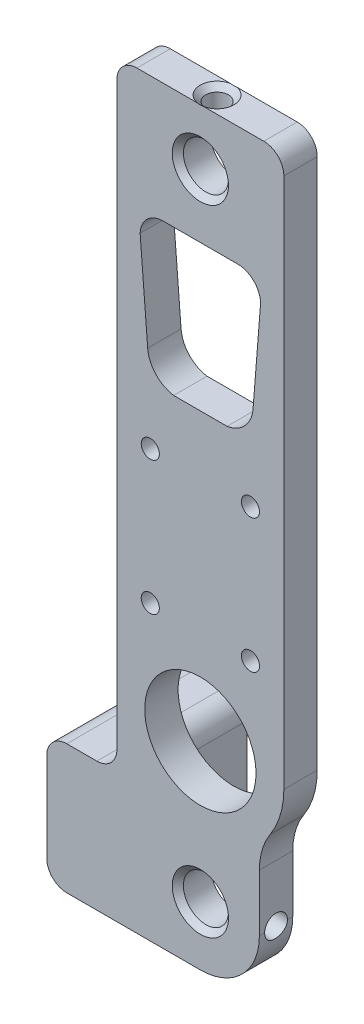
SolidWorks part; units mm, degrees
material "ABS"
ref_plane "Front Plane" through (0, 0, 0) normal (0, 0, 1) x (1, 0, 0)
ref_plane "Top Plane" through (0, 0, 0) normal (0, 1, 0) x (1, 0, 0)
ref_plane "Right Plane" through (0, 0, 0) normal (1, 0, 0) x (0, 0, -1)
sketch "Sketch1" plane through (0, 0, 0) normal (0, 0, 1) x (1, 0, 0)
  line L1 (-9, -12) -> (9, -12) construction
  line L2 (-9, -12) -> (-9, 12) construction
  line L3 (-9, 12) -> (9, 12) construction
  line L4 (9, -12) -> (9, 12) construction
  line L5 (-9, -12) -> (9, 12) construction
  line L6 (-9, 12) -> (9, -12) construction
  line L7 (-15, 17) -> (15, 17)
  line L8 (-15, 17) -> (-15, -17)
  line L9 (-15, -17) -> (15, -17)
  line L10 (15, 17) -> (15, -17)
  line L11 (-15, 17) -> (15, -17) construction
  line L12 (-15, -17) -> (15, 17) construction
  circle A0 centre (-9, 12) radius 1.625
  circle A1 centre (9, 12) radius 1.625
  circle A2 centre (-9, -12) radius 1.625
  circle A3 centre (9, -12) radius 1.625
  point P0 (0, 0)
  point P6 (0, 0)
  dimension "D5" = 3.25
  dimension "D1" = 30
  dimension "D2" = 34
  dimension "D3" = 5
  dimension "D4" = 6
extrude "Boss-Extrude1" add sketch "Sketch1" against normal blind 6
sketch "Sketch2" plane through (0, 0, 0) normal (0, 0, 1) x (1, 0, 0)
  line L1 (-15, -17) -> (15, -17)
  line L2 (-15, -17) -> (-15, -41.4)
  line L3 (-15, -64.6) -> (15, -64.6)
  line L4 (15, -17) -> (15, -64.6)
  line L5 (15, -17) -> (15, 17) construction
  line L11 (-15, -64.6) -> (-27.6, -64.6)
  line L13 (-15, -41.4) -> (-27.6, -41.4)
  line L14 (-27.6, -64.6) -> (-27.6, -41.4)
  circle A0 centre (0, -29) radius 10
  circle A1 centre (0, -54) radius 4.05
  circle A3 centre (0, -54) radius 4 construction
  circle A4 centre (0, -29) radius 9.36 construction
  dimension "D2" = 20
  dimension "D3" = 8.1
  dimension "D1" = 47.6
  dimension "D4" = 23.2
  dimension "D5" = 12.6
extrude "Boss-Extrude3" add sketch "Sketch2" along normal up to surface (-6 mm away) up to face at (10.625, -12, -6)
sketch "Sketch3" plane through (0, 0, -6) normal (0, 0, -1) x (-1, 0, 0)
  line L0 (19.7, -64.6) -> (24, -64.6) construction
  line L1 (27.6, -61) -> (27.6, -45) construction
  line L2 (24, -41.4) -> (19.7, -41.4) construction
  line L3 (19.7, -64.6) -> (24, -64.6)
  line L4 (27.6, -61) -> (27.6, -45)
  line L5 (24, -41.4) -> (19.7, -41.4)
  line L6 (19.7, -41.4) -> (19.7, -64.6)
  arc A0 (24, -64.6) -> (27.6, -61) centre (24, -61) ccw construction
  arc A1 (27.6, -45) -> (24, -41.4) centre (24, -45) ccw construction
  arc A2 (24, -64.6) -> (27.6, -61) centre (24, -61) ccw
  arc A3 (27.6, -45) -> (24, -41.4) centre (24, -45) ccw
  circle A4 centre (24, -45) radius 2.4 construction
  circle A5 centre (24, -45) radius 2.4 construction
  circle A6 centre (24, -61) radius 2.4 construction
  circle A7 centre (24, -61) radius 2.4 construction
  circle A8 centre (24, -45) radius 2.1
  circle A9 centre (24, -61) radius 2.1
  dimension "D1" = 4.2
  dimension "D2" = 23.2
extrude "Boss-Extrude4" add sketch "Sketch3" along normal up to surface (21.3764 mm away) contours L4 A3 L5 L6 L3 A2 A9 A8 region at (-23.4687, -53, -6)
sketch "Sketch4" plane through (0, 0, -6) normal (0, 0, -1) x (-1, 0, 0)
  line L2 (24, -64.6) -> (27.6, -64.6)
  line L3 (24, -64.6) -> (27.6, -64.6)
  line L4 (27.6, -64.6) -> (27.6, -61)
  line L5 (24, -41.4) -> (19.7, -41.4)
  line L6 (27.6, -45) -> (27.6, -41.4)
  line L7 (27.6, -45) -> (27.6, -41.4)
  line L9 (19.7, -41.4) -> (19.7, -64.6)
  line L11 (27.6, -61) -> (27.6, -45)
  line L13 (19.7, -41.4) -> (19.7, -64.6)
  line L15 (27.6, -61) -> (27.6, -45)
  line L18 (27.6, -64.6) -> (27.6, -61)
  line L19 (27.6, -41.4) -> (24, -41.4)
  line L22 (24, -41.4) -> (19.7, -41.4)
  line L24 (27.6, -41.4) -> (24, -41.4)
  line L27 (19.7, -64.6) -> (24, -64.6)
  line L30 (19.7, -64.6) -> (24, -64.6)
  arc A1 (24, -64.6) -> (27.6, -61) centre (24, -61) ccw
  arc A2 (24, -64.6) -> (27.6, -61) centre (24, -61) ccw
  arc A3 (27.6, -45) -> (24, -41.4) centre (24, -45) ccw
  arc A4 (27.6, -45) -> (24, -41.4) centre (24, -45) ccw
  arc A5 (24, -64.6) -> (27.6, -61) centre (24, -61) ccw
  arc A6 (27.6, -45) -> (24, -41.4) centre (24, -45) ccw
  arc A7 (24, -64.6) -> (27.6, -61) centre (24, -61) ccw
  arc A9 (27.6, -45) -> (24, -41.4) centre (24, -45) ccw
  arc M13 (27.6, -61) -> (24, -64.6) centre (24, -61) cw
  line M14 (24, -64.6) -> (27.6, -64.6)
  line M15 (27.6, -64.6) -> (27.6, -61)
  dimension "D1" = 0
  dimension "D2" = 0
  dimension "D3" = 0
extrude "Cut-Extrude1" cut sketch "Sketch4" against normal blind 10 contours A6 L7 L24 | M15 M13 M14 region at (-26.7959, -63.7959, -6) region at (-26.7959, -42.2041, -6)
sketch "Sketch5" plane through (0, 0, -6) normal (0, 0, -1) x (-1, 0, 0)
  line L0 (-15, -64.6) -> (19.7, -64.6) construction
  line L1 (19.7, -41.4) -> (15, -41.4)
  line L2 (19.7, -41.4) -> (19.7, -64.6)
  line L3 (19.7, -64.6) -> (15, -64.6)
  line L4 (15, -41.4) -> (15, -64.6)
  line L6 (15, 17) -> (15, -41.4) construction
  line L7 (19.7, -41.4) -> (15, -41.4) construction
  line L8 (19.7, -41.4) -> (19.7, -64.6) construction
  line M3 (19.7, -64.6) -> (19.7, -41.4)
  line M8 (-15, -64.6) -> (19.7, -64.6)
extrude "Boss-Extrude5" add sketch "Sketch5" along normal up to surface (17.3764 mm away) contours L1 L4 M8 M3 region at (-17.35, -53, -6)
sketch "Sketch7" plane through (0, 0, -6) normal (0, 0, -1) x (-1, 0, 0)
  line L0 (-15, -64.6) -> (-15, 17) construction
  line L3 (-10.6, -54) -> (-10.6, -43.7563)
  line L4 (-15, -64.6) -> (15, -64.6) construction
  arc A1 (-10.6, -43.7563) -> (-12.5505, -37.2149) centre (-22.5443, -43.7563) ccw
  circle A2 centre (0, -29) radius 10 construction
  circle A3 centre (0, -29) radius 15
  circle A6 centre (0, -54) radius 10.6
  line M12 (-15, 17) -> (-15, -64.6)
  line M13 (-15, -64.6) -> (15, -64.6)
extrude "Cut-Extrude2" cut sketch "Sketch7" against normal blind 10 contours A6 L3 A1 A3 M12 M13 region at (12.161, -52.411, -6)
sketch "Sketch8" plane through (10.6, 0, 0) normal (1, 0, 0) x (0, 0, -1)
  line L0 (0, -54) -> (6, -54) construction
  circle A0 centre (3, -54) radius 2.05
  dimension "D1" = 4.1
extrude "Cut-Extrude3" cut sketch "Sketch8" against normal blind 10
sketch "Sketch9" plane through (0, 0, 0) normal (0, 0, 1) x (1, 0, 0)
  line L0 (15, -29) -> (15, 17) construction
  line L1 (-15, 17) -> (15, 17)
  line L2 (-15, 17) -> (-15, 70.05)
  line L3 (-15, 70.05) -> (15, 70.05)
  line L4 (15, 17) -> (15, 70.05)
  line L5 (-6.7067, 48.5938) -> (6.7067, 48.5938)
  line L6 (10.8248, 44.6227) -> (9.4663, 27.4233)
  line L7 (4.7999, 22.3979) -> (-4.7999, 22.3979)
  line L8 (0, 22.3979) -> (0, 48.5938) construction
  line L9 (-10.8248, 44.6227) -> (-9.4663, 27.4233)
  circle A0 centre (0, 60) radius 4.05
  circle A1 centre (0, -54) radius 4.05 construction
  arc A2 (6.7067, 48.5938) -> (10.8248, 44.6227) centre (6.7067, 44.4729) cw
  arc A3 (9.4663, 27.4233) -> (4.7999, 22.3979) centre (3.9586, 27.8584) cw
  arc A4 (-6.7067, 48.5938) -> (-10.8248, 44.6227) centre (-6.7067, 44.4729) ccw
  arc A5 (-9.4663, 27.4233) -> (-4.7999, 22.3979) centre (-3.9586, 27.8584) ccw
  dimension "D1" = 6
  dimension "D2" = 60
extrude "Boss-Extrude6" add sketch "Sketch9" against normal up to surface (6 mm away) up to face at (10.625, -12, -6)
sketch "Sketch10" plane through (0, 70.05, 0) normal (0, 1, 0) x (1, 0, 0)
  line L0 (-15, 6) -> (15, 6) construction
  line L1 (15, 6) -> (15, 0) construction
  circle A0 centre (0, 3) radius 2.05
  point P4 (0, 6)
  point P7 (15, 3)
  dimension "D1" = 4.1
extrude "Cut-Extrude7" cut sketch "Sketch10" against normal blind 10
fillet "Fillet2" radius 3.6 3 edges at (-15, -41.4, -3) (15, 70.05, -3) (-15, 70.05, -3)
fillet "Fillet3" radius 3.6 1 edges at (-15, -41.4, -14.6882)
chamfer "Chamfer1" distance 1 angle 45 3 edges at (-21.9, -61, -27.3764) (-21.9, -45, -27.3764) (0, 70.05, -0.95)
chamfer "Chamfer2" distance 1 angle 45 2 edges at (4.05, -54, 0) (4.05, 60, 0)
